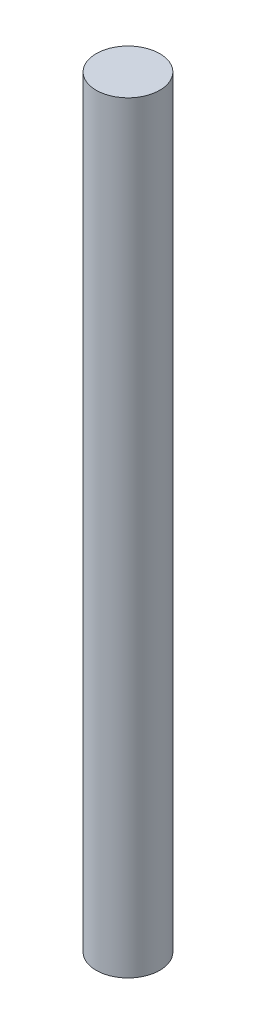
SolidWorks part; units mm, degrees
material "Alumina"
ref_plane "Front Plane" through (0, 0, 0) normal (0, 0, 1) x (1, 0, 0)
ref_plane "Top Plane" through (0, 0, 0) normal (0, 1, 0) x (1, 0, 0)
ref_plane "Right Plane" through (0, 0, 0) normal (1, 0, 0) x (0, 0, -1)
sketch "Sketch1" plane through (0, 0, 0) normal (0, 1, 0) x (1, 0, 0)
  line L1 (-1.5, 2) -> (1.5, 2)
  arc A0 (-1.5, 2) -> (1.5, 2) centre (0, 0) ccw
  dimension "D1" = 2.5
  dimension "D2" = 2
extrude "Boss-Extrude1" add sketch "Sketch1" along normal blind 15
sketch "Sketch2" plane through (0, 15, 0) normal (0, 1, 0) x (1, 0, 0)
  circle A0 centre (0, 0) radius 2.5
extrude "Boss-Extrude2" add sketch "Sketch2" along normal blind 45
